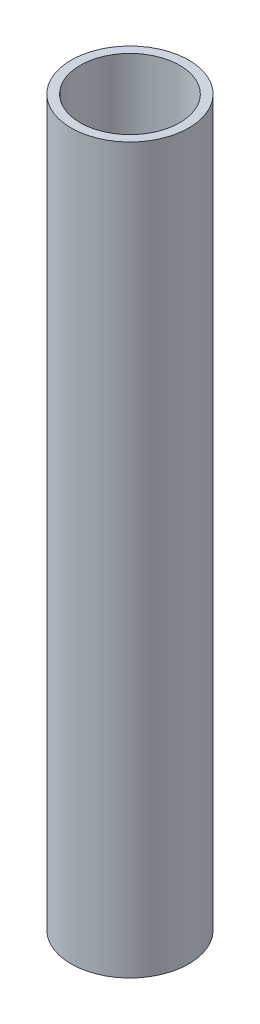
SolidWorks part; units mm, degrees
ref_plane "前视基准面" through (0, 0, 0) normal (0, 0, 1) x (1, 0, 0)
ref_plane "上视基准面" through (0, 0, 0) normal (0, 1, 0) x (1, 0, 0)
ref_plane "右视基准面" through (0, 0, 0) normal (1, 0, 0) x (0, 0, -1)
sketch "草图1" plane through (0, 0, 0) normal (0, 1, 0) x (1, 0, 0)
  circle A0 centre (0, 0) radius 16.5
  circle A1 centre (0, 0) radius 19.5
  dimension "D1" = 39
  dimension "D2" = 3
extrude "凸台-拉伸1" add sketch "草图1" along normal blind 240
